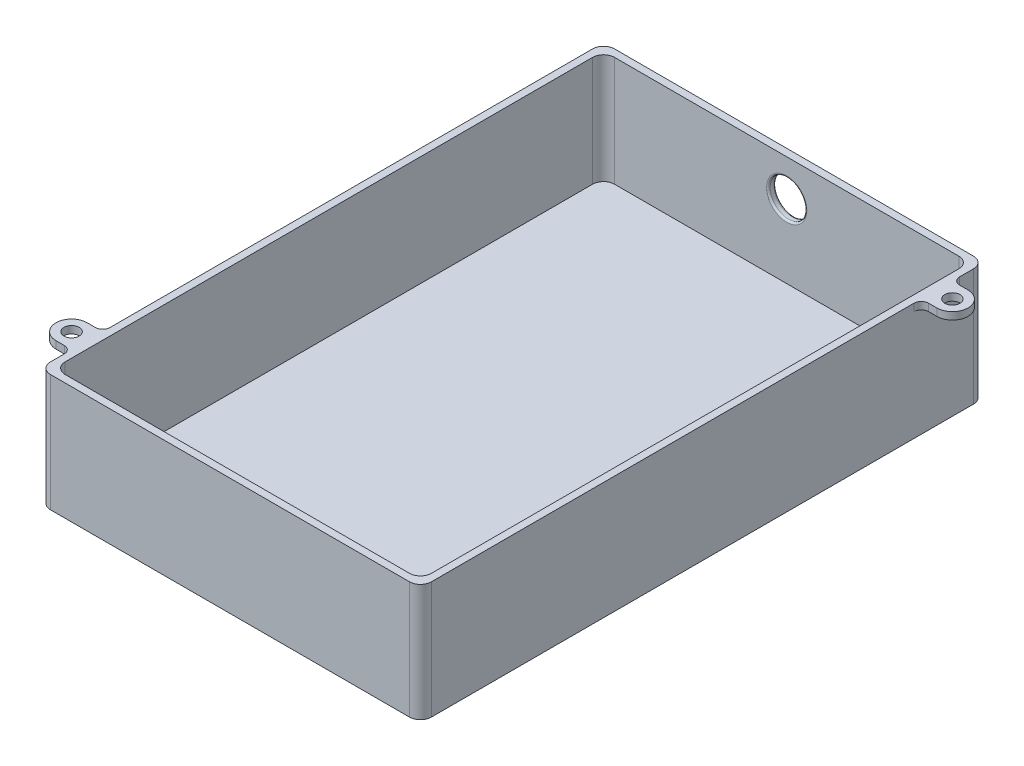
SolidWorks part; units mm, degrees
ref_plane "Front Plane" through (0, 0, 0) normal (0, 0, 1) x (1, 0, 0)
ref_plane "Top Plane" through (0, 0, 0) normal (0, 1, 0) x (1, 0, 0)
ref_plane "Right Plane" through (0, 0, 0) normal (1, 0, 0) x (0, 0, -1)
sketch "Sketch1" plane through (0, 0, 0) normal (0, 1, 0) x (1, 0, 0)
  line L0 (-52, 77) -> (52, 77)
  line L1 (-50, -75) -> (50, -75)
  line L2 (-50, -75) -> (-50, 75)
  line L3 (-50, 75) -> (50, 75)
  line L4 (50, -75) -> (50, 75)
  line L5 (-50, -75) -> (50, 75) construction
  line L6 (-50, 75) -> (50, -75) construction
  line L7 (52, -77) -> (52, 77)
  line L8 (-52, -77) -> (52, -77)
  line L9 (-52, -77) -> (-52, 77)
  point P0 (0, 0)
  dimension "D1" = 2
extrude "Boss-Extrude1" add sketch "Sketch1" along normal blind 30
extrude "Boss-Extrude2" add sketch "Sketch1<2>" against normal blind 2 contours L1 L4 L3 L2 | L9 L8 L7 L0 L4 L1 L2 L3 region at (0, 0, -75.1417) region at (0, 0, 0)
sketch "Sketch1<2>" plane through (0, 0, 0) normal (0, 1, 0) x (1, 0, 0) same geometry as "Sketch1"
fillet "Fillet1" radius 3 8 edges at (52, 14, -77) (52, 14, 77) (-52, 14, 77) (-52, 14, -77) (-50, 15, 75) (-50, 15, -75) (50, 15, -75) (50, 15, 75)
sketch "Sketch2" plane through (0, 30, 0) normal (0, 1, 0) x (1, 0, 0)
  line L0 (52, 74) -> (52, 68.25) construction
  line L2 (50, 64) -> (52, 64) construction
  line L6 (50, 68.25) -> (50, 59.75) construction
  line L7 (50, -72) -> (50, 72) construction
  line L8 (52, -74) -> (52, 74) construction
  line L9 (50, 68.25) -> (45.75, 68.25) construction
  line L10 (50, 59.75) -> (45.75, 59.75) construction
  line L11 (52, 64) -> (52, 74) construction
  line L13 (56.25, 68.25) -> (52, 68.25)
  line L14 (56.25, 59.75) -> (52, 59.75)
  line L15 (52, 59.75) -> (52, 68.25)
  circle A2 centre (45.75, 64) radius 2.075 construction
  arc A3 (45.75, 68.25) -> (45.75, 59.75) centre (45.75, 64) ccw construction
  circle A4 centre (56.25, 64) radius 2.075
  arc A5 (56.25, 59.75) -> (56.25, 68.25) centre (56.25, 64) ccw
extrude "Boss-Extrude3" add sketch "Sketch2" against normal blind 2
sketch "Sketch3" plane through (0, 30, 0) normal (0, 1, 0) x (1, 0, 0)
  line L0 (-52, -74) -> (-52, -64) construction
  line L1 (-52, 74) -> (-52, -74) construction
  line L2 (-52, -64) -> (-50, -64) construction
  line L3 (-50, 72) -> (-50, -72) construction
  line L5 (-45.75, -59.75) -> (-50, -59.75) construction
  line L6 (-50, 72) -> (-50, -72) construction
  line L7 (-50, -59.75) -> (-50, -64) construction
  line L8 (-45.75, -68.25) -> (-50, -68.25) construction
  line L9 (-50, -68.25) -> (-50, -59.75) construction
  line L10 (-56.25, -59.75) -> (-52, -59.75)
  line L11 (-56.25, -68.25) -> (-52, -68.25)
  line L12 (-52, -68.25) -> (-52, -59.75)
  circle A0 centre (-45.75, -64) radius 2.075 construction
  arc A1 (-45.75, -68.25) -> (-45.75, -59.75) centre (-45.75, -64) ccw construction
  arc A2 (-56.25, -59.75) -> (-56.25, -68.25) centre (-56.25, -64) ccw
  circle A3 centre (-56.25, -64) radius 2.075
  line M7 (-52, 74) -> (-52, -74)
extrude "Boss-Extrude4" add sketch "Sketch3" against normal blind 2 contours L10 A2 L11 A3 M7 region at (-54.125, 30, 59.8702)
sketch "Sketch4" plane through (0, 0, -77) normal (0, 0, -1) x (-1, 0, 0)
  line L0 (0, -2) -> (0, 0) construction
  line L1 (49, -2) -> (-49, -2) construction
  line L3 (0, 30) -> (0, 20) construction
  line L4 (-49, 30) -> (49, 30) construction
  circle A0 centre (0, 20) radius 7.9375
  circle A1 centre (0, 20) radius 5
extrude "Cut-Extrude1" cut sketch "Sketch4" against normal blind 10 contours A1 region at (0, 20, -77)
sketch "Sketch5" plane through (0, 30, 0) normal (0, 1, 0) x (1, 0, 0)
  line L10 (52, -74) -> (52, 59.75)
  line L11 (52, 59.75) -> (56.25, 59.75)
  line L12 (56.25, 68.25) -> (52, 68.25)
  line L13 (52, 68.25) -> (52, 74)
  line L14 (49, 77) -> (-49, 77)
  line L15 (-52, 74) -> (-52, -59.75)
  line L16 (-52, -59.75) -> (-56.25, -59.75)
  line L17 (-56.25, -68.25) -> (-52, -68.25)
  line L18 (-52, -68.25) -> (-52, -74)
  line L19 (-49, -77) -> (49, -77)
  line L20 (52, -74) -> (52, 59.75)
  line L21 (52, 59.75) -> (56.25, 59.75)
  line L22 (56.25, 68.25) -> (52, 68.25)
  line L23 (52, 68.25) -> (52, 74)
  line L24 (49, 77) -> (-49, 77)
  line L25 (-52, 74) -> (-52, -59.75)
  line L26 (-52, -59.75) -> (-56.25, -59.75)
  line L27 (-56.25, -68.25) -> (-52, -68.25)
  line L28 (-52, -68.25) -> (-52, -74)
  line L29 (-49, -77) -> (49, -77)
  arc A6 (56.25, 59.75) -> (56.25, 68.25) centre (56.25, 64) ccw
  arc A7 (52, 74) -> (49, 77) centre (49, 74) ccw
  arc A8 (-49, 77) -> (-52, 74) centre (-49, 74) ccw
  arc A9 (-56.25, -59.75) -> (-56.25, -68.25) centre (-56.25, -64) ccw
  arc A10 (-52, -74) -> (-49, -77) centre (-49, -74) ccw
  arc A11 (49, -77) -> (52, -74) centre (49, -74) ccw
  arc A12 (56.25, 59.75) -> (56.25, 68.25) centre (56.25, 64) ccw
  arc A13 (52, 74) -> (49, 77) centre (49, 74) ccw
  arc A14 (-49, 77) -> (-52, 74) centre (-49, 74) ccw
  arc A15 (-56.25, -59.75) -> (-56.25, -68.25) centre (-56.25, -64) ccw
  arc A16 (-52, -74) -> (-49, -77) centre (-49, -74) ccw
  arc A17 (49, -77) -> (52, -74) centre (49, -74) ccw
  dimension "D1" = 0
fillet "Fillet2" radius 0.5 2 edges at (5, 20, -75) (-5, 20, -77)
fillet "Fillet3" radius 2 4 edges at (-52, 29, 68.25) (-52, 29, 59.75) (52, 29, -68.25) (52, 29, -59.75)
